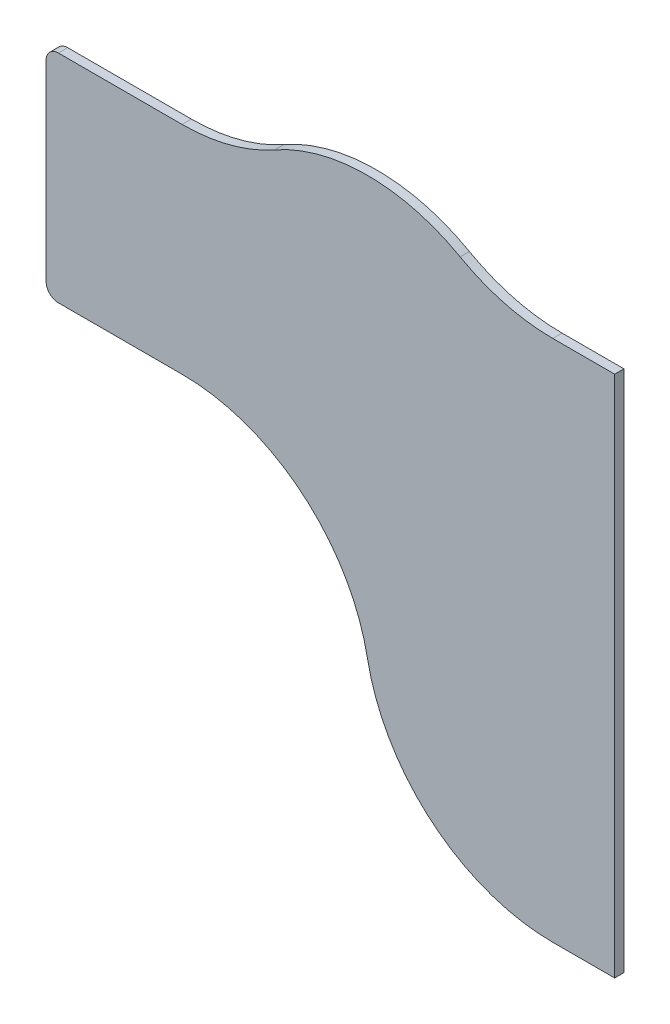
SolidWorks part; units mm, degrees
ref_plane "Front Plane" through (0, 0, 0) normal (0, 0, 1) x (1, 0, 0)
ref_plane "Top Plane" through (0, 0, 0) normal (0, 1, 0) x (1, 0, 0)
ref_plane "Right Plane" through (0, 0, 0) normal (1, 0, 0) x (0, 0, -1)
sketch "Sketch1" plane through (0, 0, 0) normal (0, 0, 1) x (1, 0, 0)
  line L0 (4.7625, 55.5625) -> (-26.9875, 55.5625)
  line L1 (4.7625, -244.7446) -> (4.7625, 87.3125) construction
  line L2 (-217.3605, 55.5625) -> (-287.2105, 55.5625)
  line L3 (4.7625, 87.3125) -> (-249.1105, 87.3125) construction
  line L4 (-217.3605, 55.5625) -> (-26.9875, 55.5625) construction
  line L6 (4.7625, -212.9946) -> (-26.9875, -212.9946)
  line L7 (0, 0) -> (-287.2105, 0) construction
  line L8 (-287.2105, -55.5625) -> (-217.3605, -55.5625)
  line L10 (-287.2105, 55.5625) -> (-287.2105, -55.5625)
  line L11 (4.7625, 55.5625) -> (4.7625, -212.9946)
  arc A0 (-26.9875, 55.5625) -> (-74.5807, 68.0544) centre (-26.9875, 152.4721) cw
  arc A1 (-74.5807, 68.0544) -> (-169.7672, 68.0544) centre (-122.174, -16.3634) ccw
  arc A2 (-169.7672, 68.0544) -> (-217.3605, 55.5625) centre (-217.3605, 152.4721) cw
  arc A3 (-217.3605, -55.5625) -> (-122.174, -134.2785) centre (-217.3605, -152.4721) cw
  arc A4 (-26.9875, -212.9946) -> (-122.174, -134.2785) centre (-26.9875, -116.085) cw
  point P14 (-122.174, 80.5462)
  point P18 (4.7625, -212.9946)
  dimension "D5" = 38.1
  dimension "D1" = 31.75
  dimension "D2" = 4.7625
  dimension "D3" = 31.75
  dimension "D4" = 31.75
  dimension "D6" = 31.75
extrude "Extrude1" add sketch "Sketch1" against normal blind 4.7625
fillet "Fillet1" radius 6.35 2 edges at (-287.2105, -55.5625, -2.3813) (-287.2105, 55.5625, -2.3813)
